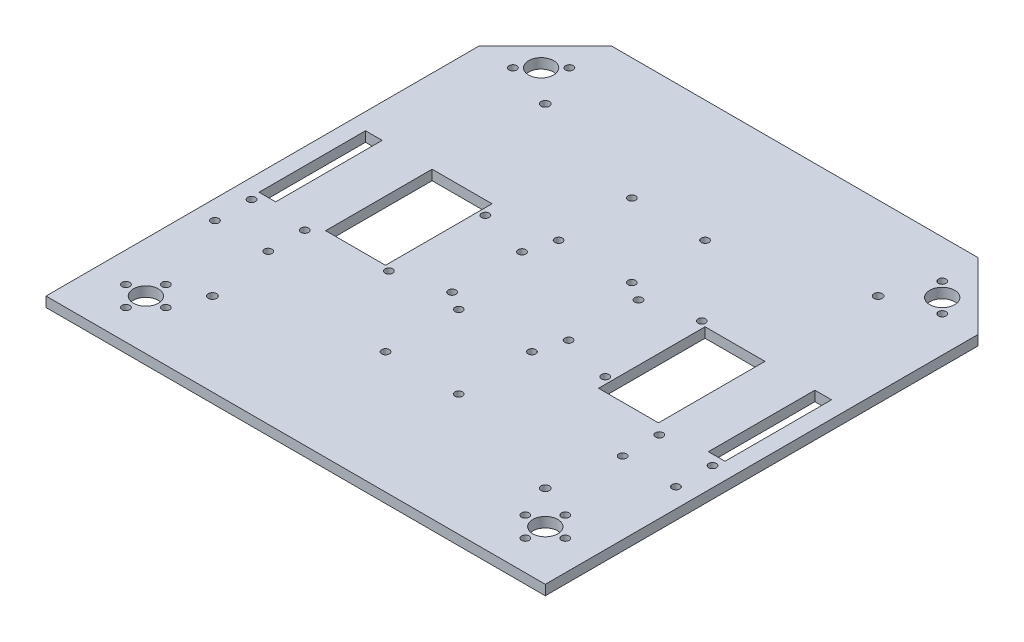
SolidWorks part; units mm, degrees
ref_plane "Plan de face" through (0, 0, 0) normal (0, 0, 1) x (1, 0, 0)
ref_plane "Plan de dessus" through (0, 0, 0) normal (0, 1, 0) x (1, 0, 0)
ref_plane "Plan de droite" through (0, 0, 0) normal (1, 0, 0) x (0, 0, -1)
sketch "Esquisse1" plane through (0, 0, 0) normal (0, 1, 0) x (1, 0, 0)
  line L0 (-150, 0) -> (-150, 260)
  line L2 (150, 0) -> (150, 260)
  line L3 (-150, 260) -> (-110, 260) construction
  line L4 (-110, 260) -> (-110, 300) construction
  line L5 (150, 260) -> (110, 260) construction
  line L6 (110, 260) -> (110, 300) construction
  line L8 (-150, 260) -> (-110, 300)
  line L9 (-110, 300) -> (110, 300)
  line L10 (0, 0) -> (0, 300) construction
  line L11 (110, 300) -> (150, 260)
  line L12 (-150, 0) -> (-120, 0) construction
  line L13 (-120, 18) -> (-120, 0) construction
  line L14 (150, 0) -> (120, 0) construction
  line L15 (120, 18) -> (120, 0) construction
  line L17 (-150, 260) -> (-120, 260) construction
  line L18 (-120, 260) -> (-120, 267.5) construction
  line L19 (150, 260) -> (120, 260) construction
  line L20 (120, 260) -> (120, 268.5) construction
  line L21 (-120, 267.5) -> (-111.5147, 275.9853) construction
  line L22 (-120, 267.5) -> (-128.4853, 259.0147) construction
  line L23 (120, 268.5) -> (128.4853, 260.0147) construction
  line L24 (120, 268.5) -> (111.5147, 276.9853) construction
  line L25 (-150, 0) -> (150, 0) construction
  line L26 (120, 30) -> (120, 18) construction
  line L27 (120, 30) -> (120, 42) construction
  line L28 (-150, 0) -> (150, 0)
  line L29 (-120, 18) -> (-120, 30) construction
  line L30 (-120, 30) -> (-120, 42) construction
  line L32 (150, 150) -> (-150, 150) construction
  line L33 (-120, 30) -> (-108, 30) construction
  line L34 (-120, 30) -> (-132, 30) construction
  line L35 (120, 30) -> (132, 30) construction
  line L36 (120, 30) -> (108, 30) construction
  circle A2 centre (-120, 30) radius 7.5
  circle A4 centre (-120, 267.5) radius 7.5
  circle A5 centre (120, 268.5) radius 7.5
  circle A6 centre (-111.5147, 275.9853) radius 2.3
  circle A7 centre (-128.4853, 259.0147) radius 2.3
  circle A8 centre (111.5147, 276.9853) radius 2.3
  circle A9 centre (128.4853, 260.0147) radius 2.3
  circle A10 centre (120, 30) radius 7.5
  circle A11 centre (120, 42) radius 2.3
  circle A13 centre (-120, 42) radius 2.3
  circle A14 centre (-120, 18) radius 2.3
  circle A16 centre (-132, 30) radius 2.3
  circle A17 centre (-108, 30) radius 2.3
  circle A18 centre (108, 30) radius 2.3
  circle A19 centre (132, 30) radius 2.3
  circle A20 centre (120, 18) radius 2.3
extrude "Boss.-Extru.1" add sketch "Esquisse1" along normal blind 6
sketch "Esquisse7" plane through (0, 6, 0) normal (0, 1, 0) x (1, 0, 0)
  line L0 (0, 150) -> (-130, 150) construction
  line L1 (0, 0) -> (0, 300) construction
  line L2 (150, 150) -> (-150, 150) construction
  line L3 (-130, 150) -> (-130, 182)
  line L4 (-130, 182) -> (-140, 182)
  line L5 (-140, 182) -> (-140, 118)
  line L6 (-140, 118) -> (-130, 118)
  line L7 (-130, 118) -> (-130, 150)
extrude "Enlèv. mat.-Extru.9" cut sketch "Esquisse7" against normal blind 10.5
sketch "Esquisse6" plane through (0, 6, 0) normal (0, 1, 0) x (1, 0, 0)
  line L0 (-142.5, 116) -> (-134.5, 116) construction
  line L2 (-142.5, 116) -> (-142.5, 150) construction
  line L3 (-142.5, 116) -> (-142.5, 108) construction
  line L11 (-142.5, 108) -> (-134.5, 108) construction
  line L12 (-134.5, 108) -> (-134.5, 116) construction
  line L14 (-142.5, 150) -> (-150, 150) construction
  line L15 (-142.5, 116) -> (-102.5, 116) construction
  line L16 (-102.5, 116) -> (-102.5, 108) construction
  line L17 (-102.5, 108) -> (-110.5, 108) construction
  line L18 (-110.5, 108) -> (-110.5, 116) construction
  line L19 (-110.5, 116) -> (-134.5, 116) construction
  line L20 (-134.5, 116) -> (-134.5, 86) construction
  line L21 (-134.5, 86) -> (-142.5, 86) construction
  line L22 (-142.5, 86) -> (-142.5, 94) construction
  line L23 (-142.5, 94) -> (-134.5, 94) construction
  line L24 (-134.5, 94) -> (-134.5, 86) construction
  line L25 (-134.5, 86) -> (-110.5, 86) construction
  line L26 (-110.5, 86) -> (-110.5, 94) construction
  line L27 (-110.5, 94) -> (-102.5, 94) construction
  line L28 (-102.5, 94) -> (-102.5, 86) construction
  line L29 (-102.5, 86) -> (-110.5, 86) construction
  line L30 (-102.5, 94) -> (-110.5, 86) construction
  line L31 (-110.5, 94) -> (-102.5, 86) construction
  line L32 (-142.5, 94) -> (-134.5, 86) construction
  line L33 (-142.5, 86) -> (-134.5, 94) construction
  line L34 (-142.5, 116) -> (-134.5, 108) construction
  line L35 (-142.5, 108) -> (-134.5, 116) construction
  line L71 (-110.5, 116) -> (-102.5, 108) construction
  line L72 (-110.5, 108) -> (-102.5, 116) construction
  line L73 (-110.5, 116) -> (-110.5, 86) construction
  circle A20 centre (-138.5, 90) radius 2.3
  circle A21 centre (-138.5, 112) radius 2.3
  circle A22 centre (-106.5, 112) radius 2.3
  circle A23 centre (-106.5, 90) radius 2.3
  dimension "D1" = 7.5
  dimension "D2" = 34
sketch "Esquisse4" plane through (0, 6, 0) normal (0, 1, 0) x (1, 0, 0)
  line L0 (-150, 150) -> (-100, 150) construction
  line L8 (150, 150) -> (-150, 150) construction
  line L14 (-100, 150) -> (-100, 182)
  line L15 (-100, 250) -> (-100, 50) construction
  line L16 (-100, 150) -> (-100, 118)
  line L17 (-100, 118) -> (-64, 118)
  line L18 (-64, 118) -> (-64, 182)
  line L19 (-64, 182) -> (-100, 182)
sketch "Esquisse9" plane through (0, 6, 0) normal (0, 1, 0) x (1, 0, 0)
  line L0 (-150, 0) -> (150, 0) construction
  line L1 (150, 0) -> (150, 300) construction
  line L2 (150, 300) -> (-150, 300) construction
  line L3 (-150, 300) -> (-150, 0) construction
  line L5 (-150, 0) -> (-150, 300) construction
  line L6 (150, 0) -> (0, 0) construction
  line L7 (0, 0) -> (0, 50) construction
  line L8 (0, 0) -> (0, 300) construction
  line L9 (0, 50) -> (100, 50) construction
  line L10 (100, 50) -> (100, 250) construction
  line L11 (100, 250) -> (-100, 250) construction
  line L12 (-100, 250) -> (-100, 50) construction
  line L13 (-100, 50) -> (0, 50) construction
  line L18 (100, 250) -> (94.3431, 244.3431) construction
  line L21 (-150, 0) -> (150, 300) construction
  circle A0 centre (-100, 50) radius 2.5
  circle A1 centre (100, 50) radius 2.5
  circle A2 centre (100, 250) radius 2.5
  circle A3 centre (-100, 250) radius 2.5
extrude "Enlèv. mat.-Extru.10" cut sketch "Esquisse6" against normal blind 50
extrude "Enlèv. mat.-Extru.11" cut sketch "Esquisse4" against normal blind 50
sketch "Esquisse3" plane through (0, 6, 0) normal (0, 1, 0) x (1, 0, 0)
  line L6 (-150, 150) -> (-64, 150) construction
  line L7 (-64, 118) -> (-64, 182) construction
  line L8 (-64, 150) -> (-64, 178) construction
  line L9 (-64, 178) -> (-56, 178) construction
  line L10 (-56, 178) -> (-56, 170) construction
  line L11 (-56, 170) -> (-59, 170) construction
  line L16 (-64, 150) -> (-64, 112) construction
  line L17 (-64, 112) -> (-56, 112) construction
  line L25 (-56, 112) -> (-56, 120) construction
  line L26 (-64, 120) -> (-34, 120) construction
  line L27 (-56, 170) -> (-64, 178) construction
  line L28 (-64, 178) -> (-56, 178) construction
  line L29 (-56, 178) -> (-64, 170) construction
  line L30 (-34, 120) -> (-26, 120) construction
  line L31 (-56, 112) -> (-64, 120) construction
  line L32 (-64, 120) -> (-56, 120) construction
  line L33 (-56, 120) -> (-64, 112) construction
  line L37 (-26, 120) -> (-26, 128) construction
  line L38 (-26, 128) -> (-34, 128) construction
  line L39 (-34, 128) -> (-26, 120) construction
  line L43 (-26, 120) -> (-34, 120) construction
  line L55 (150, 150) -> (64, 150) construction
  line L56 (150, 150) -> (-150, 150) construction
  line L57 (64, 150) -> (64, 170) construction
  line L58 (34, 130) -> (26, 130) construction
  line L61 (64, 150) -> (64, 130) construction
  line L62 (64, 130) -> (59, 130) construction
  line L63 (59, 130) -> (59, 165) construction
  line L66 (59, 165) -> (39, 165) construction
  line L70 (39, 165) -> (39, 130) construction
  line L72 (39, 130) -> (34, 130) construction
  line L73 (34, 130) -> (34, 180) construction
  line L74 (34, 180) -> (64, 180) construction
  line L76 (64, 180) -> (64, 130) construction
  line L77 (-34, 120) -> (-26, 128) construction
  line L78 (26, 130) -> (26, 138) construction
  line L79 (-34, 120) -> (-34, 170) construction
  line L80 (-39, 170) -> (-34, 170) construction
  line L81 (-34, 170) -> (-26, 170) construction
  line L82 (-26, 170) -> (-26, 162) construction
  line L83 (-26, 162) -> (-34, 162) construction
  line L84 (-34, 162) -> (-26, 170) construction
  line L85 (-26, 170) -> (-34, 170) construction
  line L86 (-34, 170) -> (-26, 162) construction
  line L87 (26, 138) -> (34, 138) construction
  line L88 (-59, 170) -> (-59, 138) construction
  line L89 (-59, 138) -> (-39, 138) construction
  line L90 (-39, 138) -> (-39, 170) construction
  line L91 (34, 138) -> (26, 130) construction
  line L92 (26, 130) -> (26, 138) construction
  line L93 (26, 138) -> (34, 130) construction
  line L94 (34, 130) -> (34, 180) construction
  line L95 (34, 180) -> (26, 180) construction
  line L96 (26, 180) -> (26, 172) construction
  line L97 (26, 172) -> (34, 172) construction
  line L98 (34, 172) -> (26, 180) construction
  line L99 (26, 180) -> (26, 172) construction
  line L100 (26, 172) -> (34, 180) construction
  line L101 (64, 180) -> (64, 188) construction
  line L102 (64, 188) -> (56, 188) construction
  line L103 (56, 188) -> (56, 180) construction
  line L104 (56, 180) -> (64, 188) construction
  line L105 (64, 188) -> (56, 188) construction
  line L106 (56, 188) -> (64, 180) construction
  line L107 (64, 180) -> (64, 130) construction
  line L108 (64, 130) -> (64, 122) construction
  line L109 (64, 122) -> (56, 122) construction
  line L110 (56, 122) -> (56, 130) construction
  line L111 (56, 130) -> (59, 130) construction
  line L112 (64, 122) -> (56, 130) construction
  line L113 (56, 130) -> (56, 122) construction
  line L114 (56, 122) -> (64, 130) construction
  circle A8 centre (-60, 174) radius 2.3
  circle A10 centre (-60, 116) radius 2.3
  circle A12 centre (-30, 166) radius 2.3
  circle A13 centre (-30, 124) radius 2.3
  circle A14 centre (60, 184) radius 2.3
  circle A15 centre (30, 176) radius 2.3
  circle A16 centre (30, 134) radius 2.3
  circle A17 centre (60, 126) radius 2.3
mirror "Symétrie1" about plane through (0, 0, 0) normal (1, 0, 0) of "Enlèv. mat.-Extru.9"
mirror "Symétrie2" about plane through (0, 0, 0) normal (1, 0, 0) of "Enlèv. mat.-Extru.11"
mirror "Symétrie3" about plane through (0, 0, 0) normal (1, 0, 0) of "Enlèv. mat.-Extru.10"
extrude "Enlèv. mat.-Extru.12" cut sketch "Esquisse9" against normal blind 35
extrude "Enlèv. mat.-Extru.13" cut sketch "Esquisse3" against normal blind 35
sketch "Esquisse10" plane through (0, 6, 0) normal (0, 1, 0) x (1, 0, 0)
  line L0 (0, 150) -> (0, 205) construction
  line L1 (-37, 187) -> (-51.6, 187) construction
  line L2 (-37, 187) -> (-37, 223) construction
  line L3 (0, 113) -> (37, 113) construction
  line L4 (37, 113) -> (37, 77) construction
  line L5 (37, 77) -> (-23, 77) construction
  line L6 (-23, 77) -> (-23, 113) construction
  line L7 (-23, 113) -> (37, 113) construction
  line L8 (-37, 187) -> (23, 187) construction
  line L9 (-28.9998, 231) -> (-20.9998, 231) construction
  line L10 (29, 69) -> (29, 77) construction
  line L11 (-20.9998, 231) -> (-20.9998, 223) construction
  line L12 (-20.9998, 223) -> (-28.9998, 231) construction
  line L13 (-28.9998, 231) -> (-20.9998, 231) construction
  line L14 (-20.9998, 231) -> (-28.9998, 223) construction
  line L15 (-37, 187) -> (-28.9998, 187) construction
  line L16 (29, 121) -> (29, 113) construction
  line L17 (37, 95) -> (56.6, 95) construction
  line L18 (29, 69) -> (29, 77) construction
  line L19 (29, 113) -> (-23, 113) construction
  line L20 (29, 77) -> (-23, 77) construction
  line L21 (-23, 77) -> (-23, 69) construction
  line L22 (-23, 69) -> (-15, 69) construction
  line L23 (-15, 69) -> (-15, 77) construction
  line L24 (-28.9998, 187) -> (-20.9998, 187) construction
  line L25 (29, 121) -> (21, 121) construction
  line L26 (-15, 77) -> (-23, 69) construction
  line L27 (-23, 69) -> (-23, 77) construction
  line L28 (-23, 77) -> (-15, 69) construction
  line L29 (-20.9998, 187) -> (-20.9998, 179) construction
  line L30 (-20.9998, 179) -> (-28.9998, 179) construction
  line L31 (-28.9998, 179) -> (-28.9998, 187) construction
  line L32 (-23, 113) -> (-23, 121) construction
  line L33 (-23, 121) -> (-15, 121) construction
  line L34 (-15, 121) -> (-15, 113) construction
  line L35 (-28.9998, 187) -> (-20.9998, 179) construction
  line L36 (-20.9998, 179) -> (-20.9998, 187) construction
  line L37 (23, 187) -> (23, 223) construction
  line L38 (23, 223) -> (-37, 223) construction
  line L39 (-37, 223) -> (23, 223) construction
  line L40 (23, 223) -> (23, 231) construction
  line L41 (23, 231) -> (15, 231) construction
  line L42 (0, 95) -> (37, 95) construction
  line L43 (-20.9998, 187) -> (-28.9998, 179) construction
  line L44 (15, 231) -> (23, 223) construction
  line L45 (23, 223) -> (23, 231) construction
  line L46 (-23, 121) -> (-15, 113) construction
  line L47 (0, 205) -> (-37, 205) construction
  line L48 (-15, 113) -> (-15, 121) construction
  line L49 (-15, 121) -> (-23, 113) construction
  line L50 (23, 231) -> (15, 223) construction
  line L51 (15, 223) -> (15, 231) construction
  line L52 (15, 231) -> (23, 223) construction
  line L53 (23, 223) -> (23, 187) construction
  line L54 (23, 187) -> (23, 179) construction
  line L55 (23, 179) -> (15, 179) construction
  line L56 (15, 179) -> (15, 187) construction
  line L57 (15, 187) -> (23, 179) construction
  line L58 (23, 179) -> (23, 187) construction
  line L59 (23, 187) -> (15, 179) construction
  line L64 (29, 121) -> (37, 121)
  line L71 (-28.9998, 231) -> (-28.9998, 223) construction
  line L73 (-52, 205) -> (-37, 205) construction
  line L74 (21, 121) -> (21, 113) construction
  line L75 (21, 113) -> (29, 121) construction
  line L76 (29, 121) -> (21, 121) construction
  line L77 (21, 121) -> (29, 113) construction
  line L78 (0, 0) -> (0, 300) construction
  line L79 (0, 150) -> (0, 95) construction
  line L80 (-37, 223) -> (-37, 231) construction
  line L81 (29, 69) -> (21, 69) construction
  line L82 (21, 69) -> (21, 77) construction
  line L84 (-28.9998, 223) -> (-37, 231) construction
  line L86 (21, 77) -> (29, 69) construction
  line L87 (29, 69) -> (29, 77) construction
  line L88 (29, 77) -> (21, 69) construction
  line L89 (-28.9998, 223) -> (-28.9998, 231) construction
  line L90 (-28.9998, 231) -> (-37, 223) construction
  circle A22 centre (-19, 73) radius 2.3
  circle A30 centre (-19, 117) radius 2.3
  circle A35 centre (25, 73) radius 2.3
  circle A36 centre (25, 117) radius 2.3
  circle A37 centre (-24.9998, 227) radius 2.3
  circle A39 centre (-24.9998, 183) radius 2.3
  circle A40 centre (19, 183) radius 2.3
  circle A41 centre (19, 227) radius 2.3
  point P47 (0, 0)
  point P48 (0, 0)
extrude "Enlèv. mat.-Extru.14" cut sketch "Esquisse10" against normal blind 10 contours A35 | A22 | A30 | A40 | A41 | A37 | A39 | A36 region at (-19, 6, -73) region at (-19, 6, -117) region at (25, 6, -73) region at (19, 6, -183) region at (19, 6, -227)
sketch "Esquisse11" plane through (0, 6, 0) normal (0, 1, 0) x (1, 0, 0)
  line L0 (0, 150) -> (0, 185) construction
  line L1 (0, 0) -> (0, 300) construction
  line L2 (0, 185) -> (-30, 185) construction
  line L3 (-30, 185) -> (-30, 235) construction
  line L4 (-30, 185) -> (-30, 193) construction
  line L5 (0, 150) -> (0, 115) construction
  line L6 (0, 115) -> (30, 115) construction
  line L7 (30, 107) -> (30, 72) construction
  line L8 (30, 115) -> (30, 107) construction
  line L9 (-30, 223) -> (-38, 223) construction
  line L12 (-30, 213) -> (-38, 213) construction
  circle A7 centre (30, 97) radius 2.3
  circle A9 centre (30, 77) radius 2.3
  circle A11 centre (-30, 203) radius 2.3
  circle A13 centre (-30, 223) radius 2.3
  circle A17 centre (-30, 185) radius 2.3
  circle A18 centre (30, 115) radius 2.3
  circle A19 centre (-40, 223) radius 2.3
  circle A20 centre (-50, 223) radius 2.3
  circle A21 centre (40, 77) radius 2.3
  circle A22 centre (50, 77) radius 2.3
  dimension "D1" = 3
  dimension "D2" = 3
